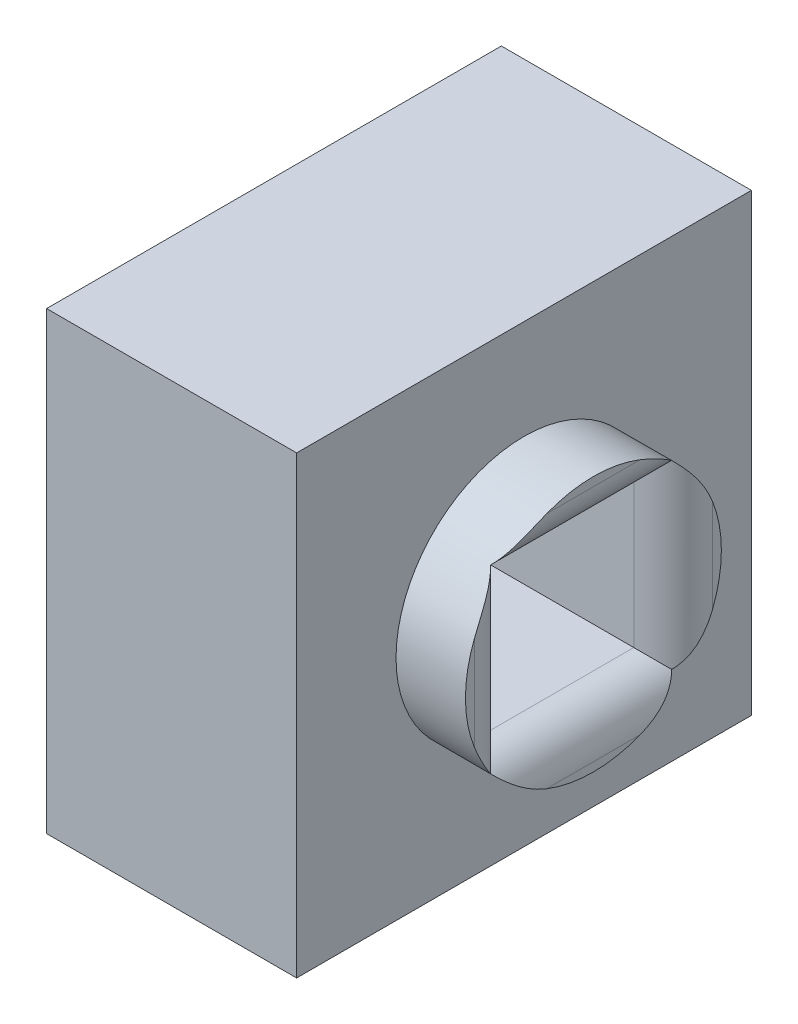
SolidWorks part; units mm, degrees
ref_plane "Front" through (0, 0, 0) normal (0, 0, 1) x (1, 0, 0)
ref_plane "Top" through (0, 0, 0) normal (0, 1, 0) x (1, 0, 0)
ref_plane "Right" through (0, 0, 0) normal (1, 0, 0) x (0, 0, -1)
sketch "Sketch2" plane through (0, 0, 0) normal (1, 0, 0) x (0, 0, -1)
  line L1 (0, 0) -> (8.1, 0)
  line L2 (0, 0) -> (0, 8.1)
  line L3 (0, 8.1) -> (8.1, 8.1)
  line L4 (8.1, 0) -> (8.1, 8.1)
  dimension "D1" = 8.1
  dimension "D2" = 8.1
extrude "Extrude-Thin1" add sketch "Sketch2" along normal blind 12.7 thin thin type one direction wall 7.5
sketch "Sketch3" plane through (12.7, 0, 0) normal (1, 0, 0) x (0, 0, -1)
  line L0 (0, 0) -> (8.1, 8.1) construction
  line L2 (0, 8.1) -> (8.1, 8.1)
  line L3 (0, 8.1) -> (0, 0)
  line L4 (0, 0) -> (8.1, 0)
  line L5 (8.1, 8.1) -> (8.1, 0)
  circle A0 centre (4.05, 4.05) radius 6.5
extrude "Boss-Extrude1" add sketch "Sketch3" along normal blind 3.525
fillet "Fillet1" radius 2 8 edges at (16.225, 4.05, 0) (16.225, 0, -4.05) (16.225, 4.05, -8.1) (16.225, 8.1, -4.05) (0, 8.1, -4.05) (0, 4.05, 0) (0, 0, -4.05) (0, 4.05, -8.1)
